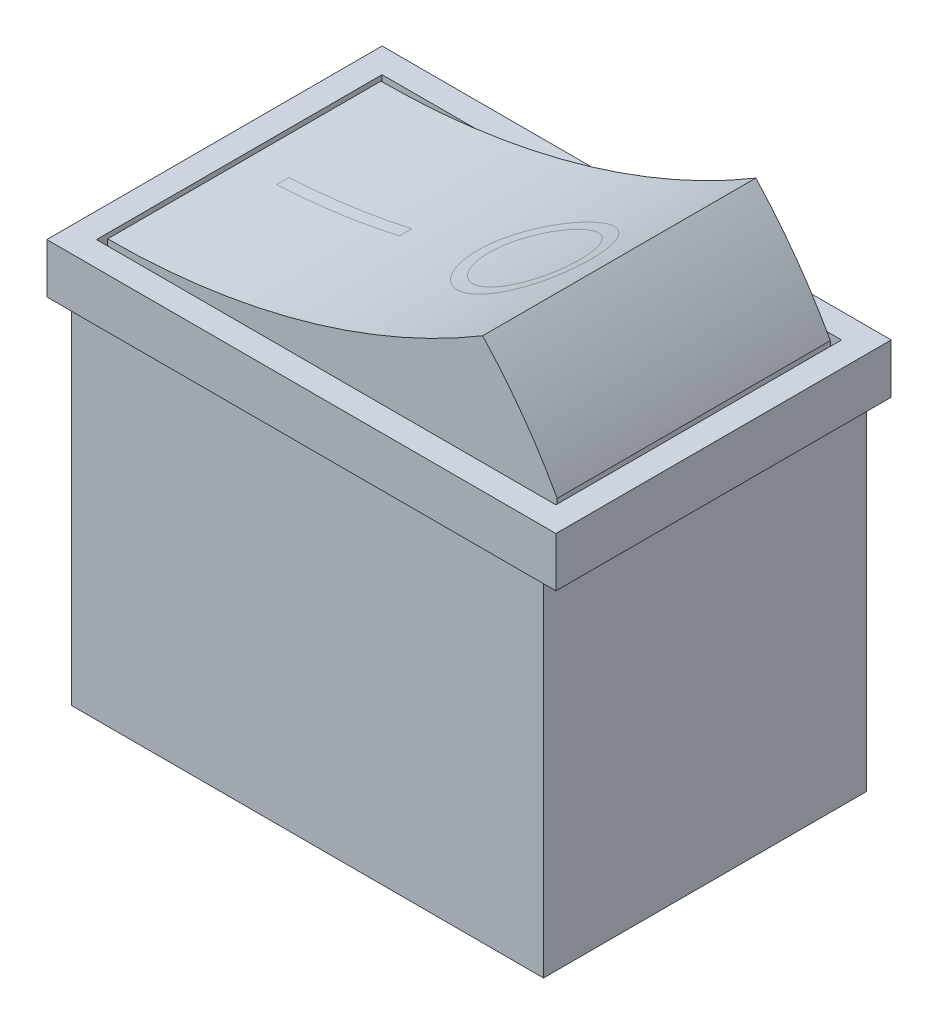
SolidWorks part; units mm, degrees
ref_plane "Front Plane" through (0, 0, 0) normal (0, 0, 1) x (1, 0, 0)
ref_plane "Top Plane" through (0, 0, 0) normal (0, 1, 0) x (1, 0, 0)
ref_plane "Right Plane" through (0, 0, 0) normal (1, 0, 0) x (0, 0, -1)
sketch "Sketch1" plane through (0, 0, 0) normal (0, 1, 0) x (1, 0, 0)
  line L1 (-9.5, -6.5) -> (9.5, -6.5)
  line L2 (-9.5, -6.5) -> (-9.5, 6.5)
  line L3 (-9.5, 6.5) -> (9.5, 6.5)
  line L4 (9.5, -6.5) -> (9.5, 6.5)
  line L5 (-9.5, -6.5) -> (9.5, 6.5) construction
  line L6 (-9.5, 6.5) -> (9.5, -6.5) construction
  point P0 (0, 0)
  dimension "D1" = 19
  dimension "D2" = 13
extrude "Boss-Extrude1" add sketch "Sketch1" along normal blind 14
sketch "Sketch2" plane through (0, 14, 0) normal (0, 1, 0) x (1, 0, 0)
  line L1 (-10.25, 6.75) -> (10.25, 6.75)
  line L2 (-10.25, 6.75) -> (-10.25, -6.75)
  line L3 (-10.25, -6.75) -> (10.25, -6.75)
  line L4 (10.25, 6.75) -> (10.25, -6.75)
  line L5 (-10.25, 6.75) -> (10.25, -6.75) construction
  line L6 (-10.25, -6.75) -> (10.25, 6.75) construction
  point P0 (0, 0)
  dimension "D1" = 20.5
  dimension "D2" = 13.5
extrude "Boss-Extrude2" add sketch "Sketch2" along normal blind 2
sketch "Sketch3" plane through (0, 16, 0) normal (0, 1, 0) x (1, 0, 0)
  line L8 (9.25, -5.75) -> (9.25, 5.75)
  line L9 (9.25, 5.75) -> (-9.25, 5.75)
  line L10 (-9.25, 5.75) -> (-9.25, -5.75)
  line L11 (-9.25, -5.75) -> (9.25, -5.75)
  line L12 (9.25, -5.75) -> (9.25, 5.75)
  line L13 (9.25, 5.75) -> (-9.25, 5.75)
  line L14 (-9.25, 5.75) -> (-9.25, -5.75)
  line L15 (-9.25, -5.75) -> (9.25, -5.75)
  dimension "D1" = 1
extrude "Cut-Extrude1" cut sketch "Sketch3" against normal blind 10
sketch "Sketch5" plane through (0, 0, 0) normal (0, 0, 1) x (1, 0, 0)
  line L0 (-9.25, 16) -> (9.25, 16) construction
  line L1 (9.25, 6) -> (9.25, 16) construction
  line L2 (-9.25, 6) -> (-9.25, 16) construction
  line L3 (9.05, 16) -> (9.05, 6)
  line L4 (-9.25, 6) -> (9.25, 6) construction
  line L5 (9.05, 6) -> (-9.05, 6)
  line L6 (-9.05, 6) -> (-9.05, 16)
  arc A0 (9.05, 16) -> (6.05, 20.1704) centre (-9.25, 6) ccw
  arc A1 (-9.05, 16) -> (6.05, 20.1704) centre (-9.05, 45.422) ccw
  dimension "D1" = 0.2
  dimension "D2" = 0.2
  dimension "D3" = 3
extrude "Boss-Extrude3" add sketch "Sketch5" along normal mid plane 11
sketch "Sketch6" plane through (0, 0, 0) normal (0, 1, 0) x (1, 0, 0)
  line L1 (-7.5, 0.25) -> (-2.5, 0.25)
  line L2 (-7.5, 0.25) -> (-7.5, -0.25)
  line L3 (-7.5, -0.25) -> (-2.5, -0.25)
  line L4 (-2.5, 0.25) -> (-2.5, -0.25)
  line L5 (-7.5, 0.25) -> (-2.5, -0.25) construction
  line L6 (-7.5, -0.25) -> (-2.5, 0.25) construction
  circle A0 centre (3, 0) radius 2.5
  circle A1 centre (3, 0) radius 2
  point P3 (-5, 0)
  dimension "D1" = 5
  dimension "D2" = 4
  dimension "D3" = 0.5
  dimension "D4" = 5
  dimension "D5" = 3
  dimension "D6" = 5
wrap "Wrap1" sketch "Sketch6" wrap type scribe source sketch "Sketch6" face at (-1.3587, 17.5735, 0)
